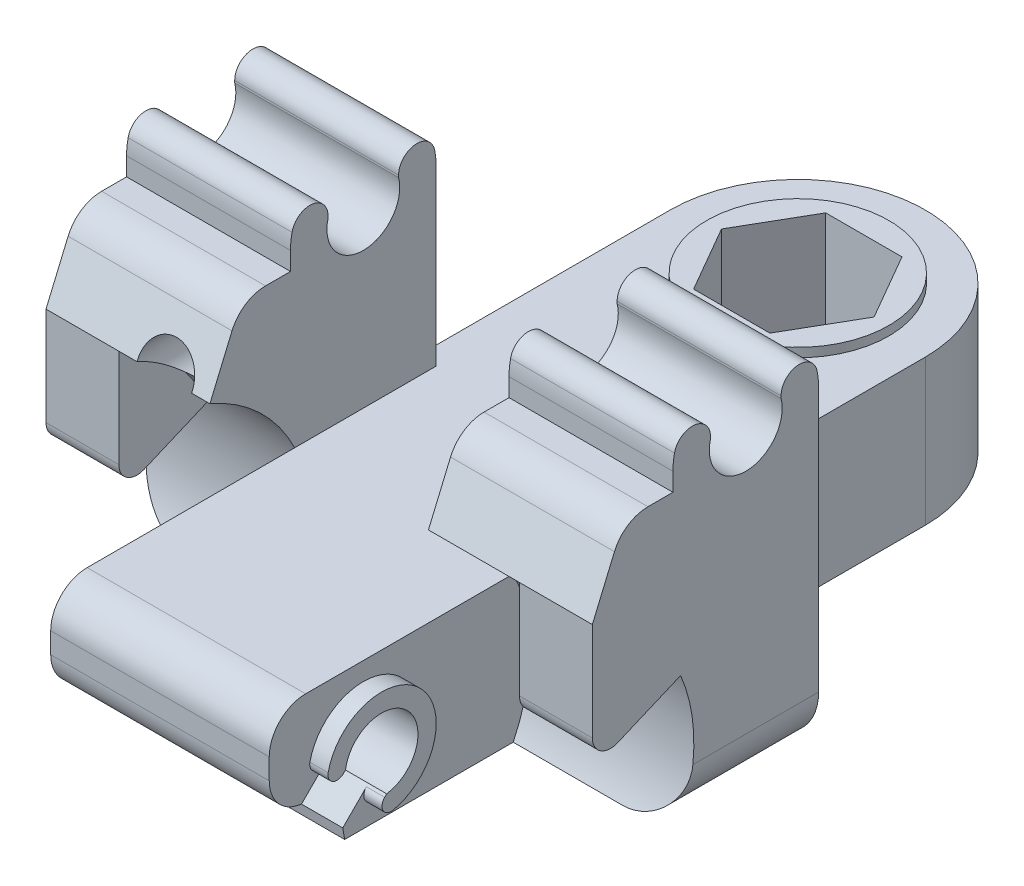
SolidWorks part; units mm, degrees
ref_plane "Front Plane" through (0, 0, 0) normal (0, 0, 1) x (1, 0, 0)
ref_plane "Top Plane" through (0, 0, 0) normal (0, 1, 0) x (1, 0, 0)
ref_plane "Right Plane" through (0, 0, 0) normal (1, 0, 0) x (0, 0, -1)
sketch "Sketch3" plane through (0, 0, 0) normal (1, 0, 0) x (0, 0, -1)
  line L0 (0.2828, -1.9799) -> (-1.9799, 0.2828)
  line L1 (0.2828, -1.9799) -> (-1.1314, -3.3941)
  line L2 (-1.1314, -3.3941) -> (-0.8188, -5.1668)
  line L3 (-0.8188, -5.1668) -> (-3.9199, -8.2678)
  line L4 (-1.9799, 0.2828) -> (-3.3941, -1.1314)
  line L5 (-3.3941, -1.1314) -> (-5.1668, -0.8188)
  line L6 (-5.1668, -0.8188) -> (-8.2678, -3.9199)
  line L7 (-0.8485, -0.8485) -> (0, 0) construction
  line L8 (0, 0) -> (-2, 0) construction
  line L9 (-1.9799, 0.2828) -> (-5.1668, -0.8188) construction
  line L10 (-0.8188, -5.1668) -> (0.2828, -1.9799) construction
  circle A0 centre (0, 0) radius 2
  circle A1 centre (0, 0) radius 8.65 construction
  circle A2 centre (0, 0) radius 9.15 construction
  circle A3 centre (0, 0) radius 9.15
  dimension "D1" = 4
  dimension "D2" = 17.3
  dimension "D4" = 0.5
  dimension "D5" = 2
  dimension "D7" = 3.2
  dimension "D6" = 1.8
  dimension "D8" = 45
  dimension "D9" = 125
extrude "Boss-Extrude1" add sketch "Sketch3" along normal mid plane 12 contours A3 L6 L5 L4 A0 L1 L2 L3 | A3 region at (0, -1.48, -1.7064)
sketch "Sketch5" plane through (0, 0, 0) normal (1, 0, 0) x (0, 0, -1)
  line L0 (0, 9.15) -> (29.856, 9.15)
  line L1 (29.856, 9.15) -> (29.856, -9.15)
  line L2 (29.856, -9.15) -> (0, -9.15)
  arc A0 (-3.9199, -8.2678) -> (-8.2678, -3.9199) centre (0, 0) ccw construction
  arc A1 (0, -9.15) -> (0, 9.15) centre (0, 0) ccw
  dimension "D1" = 29.856
extrude "Boss-Extrude2" add sketch "Sketch5" along normal mid plane 14
sketch "Sketch6" plane through (0, 9.15, 0) normal (0, 1, 0) x (1, 0, 0)
  line L0 (7, 29.856) -> (-7, 29.856) construction
  circle A0 centre (0, 29.856) radius 7
extrude "Boss-Extrude3" add sketch "Sketch6" against normal up to surface (18.3 mm away) up to face at (0, -9.15, -9.952)
sketch "Sketch7" plane through (0, 0, 0) normal (0, 1, 0) x (1, 0, 0)
  circle A0 centre (0, 29.856) radius 4.5
  dimension "D1" = 9
extrude "Boss-Extrude4" add sketch "Sketch7" along normal blind 8 and the other way blind 8
sketch "Sketch8" plane through (0, 9.15, 0) normal (0, 1, 0) x (1, 0, 0)
  line L0 (6, -9.15) -> (6, 0) construction
  line L1 (-6, 0) -> (-6, -9.15) construction
  line L3 (7, 0) -> (7, 29.856) construction
  line L4 (-7, 29.856) -> (-7, 0) construction
  line L5 (-7, 0) -> (-6, 0) construction
  line L6 (6, 0) -> (7, 0) construction
  line L7 (6, -9.15) -> (6, 0)
  line L8 (-6, 0) -> (-6, -9.15)
  line L9 (-6, -9.15) -> (6, -9.15)
  line L10 (7, 0) -> (7, 29.856)
  line L11 (-7, 29.856) -> (-7, 0)
  line L12 (-7, 0) -> (-6, 0)
  line L13 (6, 0) -> (7, 0)
  arc A0 (7, 29.856) -> (-7, 29.856) centre (0, 29.856) ccw construction
  arc A1 (7, 29.856) -> (-7, 29.856) centre (0, 29.856) ccw
  line M10 (7, 0) -> (7, 29.856)
  arc M11 (7, 29.856) -> (-7, 29.856) centre (0, 29.856) ccw
  line M12 (-7, 29.856) -> (-7, 0)
  line M13 (-7, 0) -> (-6, 0)
  line M14 (-6, 0) -> (6, 0)
  line M15 (6, 0) -> (7, 0)
extrude "Cut-Extrude2" cut sketch "Sketch8" against normal offset from surface (5.15 mm away) 4 contours M15 M10 M11 M12 M13 M14 | L8 L9 L7 M14 region at (0, 9.15, 4.575) region at (0, 9.15, -17.7114) up to plane "Top Plane"
sketch "Sketch9" plane through (0, -9.15, 0) normal (0, -1, 0) x (1, 0, 0)
  line L7 (6, 0) -> (6, 9.15)
  line L8 (7, 0) -> (6, 0)
  line L9 (7, -29.856) -> (7, 0)
  line L10 (-7, 0) -> (-7, -29.856)
  line L11 (-6, 0) -> (-7, 0)
  line L12 (-6, 9.15) -> (-6, 0)
  line L13 (6, 9.15) -> (-6, 9.15)
  line L14 (6, 0) -> (6, 9.15)
  line L15 (7, 0) -> (6, 0)
  line L16 (7, -29.856) -> (7, 0)
  line L17 (-7, 0) -> (-7, -29.856)
  line L18 (-6, 0) -> (-7, 0)
  line L19 (-6, 9.15) -> (-6, 0)
  line L20 (6, 9.15) -> (-6, 9.15)
  arc A1 (-7, -29.856) -> (7, -29.856) centre (0, -29.856) ccw
  arc A2 (-7, -29.856) -> (7, -29.856) centre (0, -29.856) ccw
  line M10 (-7, 0) -> (-7, -29.856)
  arc M11 (-7, -29.856) -> (7, -29.856) centre (0, -29.856) ccw
  line M12 (7, -29.856) -> (7, 0)
  line M13 (7, 0) -> (6, 0)
  line M14 (6, 0) -> (-6, 0)
  line M15 (-6, 0) -> (-7, 0)
  dimension "D1" = 0
extrude "Cut-Extrude4" cut sketch "Sketch9" against normal offset from surface (5.15 mm away) 4 contours M15 M10 M11 M12 M13 M14 | L14 L20 L19 M14 region at (0, -9.15, 4.575) region at (0, -9.15, -17.7114) up to plane "Top Plane"
sketch "Sketch24" plane through (-6, 0, 0) normal (-1, 0, 0) x (0, 0, 1)
  line L0 (1.9799, 0.2828) -> (2.9258, -0.6631)
  line L1 (1.9799, 0.2828) -> (3.3941, -1.1314) construction
  line L2 (-0.2828, -1.9799) -> (0.6631, -2.9258)
  line L3 (-0.2828, -1.9799) -> (1.1314, -3.3941) construction
  arc A0 (1.9799, 0.2828) -> (-0.2828, -1.9799) centre (0, 0) ccw construction
  arc A1 (1.9799, 0.2828) -> (-0.2828, -1.9799) centre (0, 0) ccw
  circle A2 centre (0, 0) radius 3
  line M5 (1.1314, -3.3941) -> (-0.2828, -1.9799)
  arc M6 (-0.2828, -1.9799) -> (1.9799, 0.2828) centre (0, 0) cw
  line M7 (1.9799, 0.2828) -> (3.3941, -1.1314)
  dimension "D1" = 6
extrude "Boss-Extrude6" add sketch "Sketch24" along normal blind 1 contours A2 M7 M5 M6 region at (-6, 1.4742, -1.4742)
fillet "Fillet3" radius 0.5 2 edges at (-6.5, -2.9258, 0.6631) (-6.5, -0.6631, 2.9258)
mirror "Mirror1" about plane through (0, 0, 0) normal (1, 0, 0) of "Fillet3", "Boss-Extrude6"
sketch "Sketch10" plane through (0, 0, 0) normal (1, 0, 0) x (0, 0, -1)
  line L3 (8.2294, -4) -> (29.856, -4)
  line L4 (29.856, -4) -> (29.856, 4)
  line L5 (29.856, 4) -> (8.2294, 4)
  line L10 (8, 12.5) -> (8, 17.5) construction
  line L11 (8, 17.5) -> (16, 17.5) construction
  line L12 (16, 17.5) -> (16, 4) construction
  line L13 (5.3059, 12.5) -> (8, 12.5)
  line L14 (0, 0) -> (3.5752, 8.4226) construction
  line L15 (3.5752, 8.4226) -> (5.3059, 12.5)
  line L16 (29.856, 4) -> (8.2294, 4) construction
  line L17 (16, 4) -> (8.2294, 4)
  line L18 (8, 13.5) -> (16, 13.5) construction
  line L19 (26, 14) -> (26, 4) construction
  line L20 (29.856, -4) -> (8.2294, -4) construction
  line L21 (10.0635, 14) -> (13.9365, 14) construction
  line L22 (13.9365, 14) -> (13.9365, 17)
  line L23 (10.0635, 17) -> (10.0635, 14)
  line L24 (8, 13.5) -> (8, 12.5)
  line L25 (16, 13.5) -> (16, 4)
  line L26 (16, -4) -> (8.2294, -4)
  line L27 (16, 4) -> (16, -4)
  arc A0 (10.0635, 14) -> (13.9365, 14) centre (12, 13.5) ccw
  arc A1 (8.2294, -4) -> (8.2294, 4) centre (0, 0) ccw
  arc A2 (8.2294, 4) -> (3.5752, 8.4226) centre (0, 0) ccw
  arc A3 (16, 13.5) -> (13.9365, 17) centre (12, 13.5) ccw
  arc A4 (10.0635, 17) -> (8, 13.5) centre (12, 13.5) ccw
  arc A5 (8.2294, -4) -> (8.2294, 4) centre (0, 0) ccw construction
  arc A6 (8.2294, -4) -> (8.2294, 4) centre (0, 0) ccw
  dimension "D8" = 4
  dimension "D9" = 2
  dimension "D10" = 2.5
  dimension "D2" = 67
  dimension "D3" = 10
  dimension "D4" = 13.5
  dimension "D5" = 5
  dimension "D6" = 12
  dimension "D7" = 5
  dimension "D1" = 0
extrude "Boss-Extrude5" add sketch "Sketch10" along normal mid plane 30 contours A6 L26 L27 L17 | L23 A4 L24 L13 L15 A2 L17 L25 A3 L22 A0 region at (0, 0, -12.4196) region at (0, 9.2496, -10.8111)
ref_plane "Plane1" through (6, 0, 0) normal (1, 0, 0) x (0, 0, -1)
ref_plane "Plane2" through (-6, 0, 0) normal (1, 0, 0) x (0, 0, -1)
sketch "Sketch13" plane through (-6, 0, 0) normal (1, 0, 0) x (0, 0, -1)
  line L0 (0, 5) -> (36.856, 5)
  line L2 (36.856, 4) -> (36.856, 5) construction
  circle A0 centre (0, 0) radius 5 construction
  dimension "D1" = 10
ref_plane "Plane3" through (0, 0, 0) normal (0, 0, 1) x (1, 0, 0)
ref_plane "Plane4" [suppressed] through (0, 0, -32.856) normal (0, 0, -1) x (-1, 0, 0)
ref_plane "Plane5" [suppressed] through (-3, 0, 0) normal (-1, 0, 0) x (0, 0, 1)
sketch "Sketch18" [suppressed] plane through (0, 0, -32.856) normal (0, 0, -1) x (-1, 0, 0)
  line L0 (0, 29) -> (0, 16) construction
  line L2 (3, 29) -> (-3, 29) construction
  circle A0 centre (0, 16) radius 1.9
  dimension "D2" = 3.8
  dimension "D1" = 13
extrude "Cut-Extrude5" [suppressed] cut sketch "Sketch18" against normal blind 1
sketch "Sketch20" plane through (0, 4, 0) normal (0, 1, 0) x (1, 0, 0)
  line L0 (0, 25.356) -> (0, 0) construction
  line L2 (-6, -16) -> (6, -16)
  line L3 (-6, -16) -> (-6, 16)
  line L4 (-6, 16) -> (6, 16)
  line L5 (6, -16) -> (6, 16)
  line L6 (-6, -16) -> (6, 16) construction
  line L7 (-6, 16) -> (6, -16) construction
  line L8 (-7, 16) -> (7, 16) construction
  dimension "D1" = 12
extrude "Cut-Extrude7" cut sketch "Sketch20" along normal through all
sketch "Sketch32" plane through (6, 0, 0) normal (1, 0, 0) x (0, 0, -1)
  line L0 (-5.1668, -0.8188) -> (-5.1668, 4)
  line L1 (8.2294, 4) -> (-8.2294, 4) construction
  line L9 (-3.3941, -1.1314) -> (-2.0905, 0.1722)
  line L10 (0.1722, -2.0905) -> (-1.1314, -3.3941)
  line L11 (-1.1314, -3.3941) -> (-1.0245, -4)
  line L12 (-1.0245, -4) -> (8.2294, -4)
  line L13 (8.2294, 4) -> (-8.2294, 4)
  line L14 (-8.2678, -3.9199) -> (-5.1668, -0.8188)
  line L15 (-5.1668, -0.8188) -> (-3.3941, -1.1314)
  line L16 (-3.3941, -1.1314) -> (-2.0905, 0.1722)
  line L17 (0.1722, -2.0905) -> (-1.1314, -3.3941)
  line L18 (-1.1314, -3.3941) -> (-1.0245, -4)
  line L19 (-1.0245, -4) -> (8.2294, -4)
  line L20 (8.2294, 4) -> (-8.2294, 4)
  line L21 (-8.2678, -3.9199) -> (-5.1668, -0.8188)
  line L22 (-5.1668, -0.8188) -> (-3.3941, -1.1314)
  arc A5 (-2.9329, 0.6309) -> (-2.0905, 0.1722) centre (-2.4441, 0.5258) ccw
  arc A6 (0.6309, -2.9329) -> (-2.9329, 0.6309) centre (0, 0) ccw
  arc A7 (0.1722, -2.0905) -> (0.6309, -2.9329) centre (0.5258, -2.4441) ccw
  arc A8 (8.2294, -4) -> (8.2294, 4) centre (0, 0) ccw
  arc A9 (-8.2294, 4) -> (-8.2678, -3.9199) centre (0, 0) ccw
  arc A10 (-2.9329, 0.6309) -> (-2.0905, 0.1722) centre (-2.4441, 0.5258) ccw
  arc A11 (0.6309, -2.9329) -> (-2.9329, 0.6309) centre (0, 0) ccw
  arc A12 (0.1722, -2.0905) -> (0.6309, -2.9329) centre (0.5258, -2.4441) ccw
  arc A13 (8.2294, -4) -> (8.2294, 4) centre (0, 0) ccw
  arc A14 (-8.2294, 4) -> (-8.2678, -3.9199) centre (0, 0) ccw
  line M21 (8.2294, 4) -> (-8.2294, 4)
  arc M22 (-8.2294, 4) -> (-8.2678, -3.9199) centre (0, 0) ccw
  line M23 (-8.2678, -3.9199) -> (-5.1668, -0.8188)
  dimension "D1" = 0
extrude "Cut-Extrude9" cut sketch "Sketch32" against normal blind 25 contours L0 M23 M21 M22 region at (6, 0.6087, 7.1825)
fillet "Fillet1" radius 2 2 edges at (0, 4, 5.1668) (0, -0.8188, 5.1668)
fillet "Fillet2" radius 1 4 edges at (-10.5, 17, -13.9365) (-10.5, 17, -10.0635) (10.5, 17, -10.0635) (10.5, 17, -13.9365)
sketch "Sketch23" plane through (0, 4, 0) normal (0, 1, 0) x (1, 0, 0)
  line L0 (-7, 29.856) -> (7, 29.856) construction
  line L1 (4.1881, 29.856) -> (2.094, 33.483)
  line L2 (2.094, 33.483) -> (-2.094, 33.483)
  line L3 (-2.094, 33.483) -> (-4.1881, 29.856)
  line L4 (-4.1881, 29.856) -> (-2.094, 26.229)
  line L5 (-2.094, 26.229) -> (2.094, 26.229)
  line L6 (2.094, 26.229) -> (4.1881, 29.856)
  line L7 (-7, 16) -> (-7, 29.856) construction
  circle A0 centre (0, 29.856) radius 3.627 construction
  dimension "D1" = 7.254
extrude "Cut-Extrude8" cut sketch "Sketch23" against normal through all
sketch "Sketch25" plane through (15, 0, 0) normal (1, 0, 0) x (0, 0, -1)
  line L0 (10.0635, 13) -> (13.9365, 13)
  arc A0 (10.0635, 14) -> (13.9365, 14) centre (12, 13.5) ccw construction
  arc A1 (10.0635, 14) -> (13.9365, 14) centre (12, 13.5) ccw
  arc M14 (13.9365, 14) -> (10.0635, 14) centre (12, 13.5) cw
  dimension "D1" = 1.5
extrude "Boss-Extrude7" [suppressed] add sketch "Sketch25" against normal blind 1 contours L0 M14
fillet "Fillet4" [suppressed] radius 0.5
mirror "Mirror2" [suppressed] about plane through (0, 0, 0) normal (1, 0, 0)
fillet "Fillet5" radius 3 2 edges at (15, -4, -12.1147) (-15, -4, -12.1147)
fillet "Fillet7" radius 2 2 edges at (-10.5, 12.5, -5.3059) (10.5, 12.5, -5.3059)
ref_plane "Plane6" through (-8.5, 0, 0) normal (-1, 0, 0) x (0, 0, 1)
sketch "Sketch27" plane through (-8.5, 0, 0) normal (-1, 0, 0) x (0, 0, 1)
  line L0 (0, 8.5) -> (-25.4214, 8.5)
  circle A0 centre (0, 0) radius 8.5 construction
  dimension "D1" = 17
sweep "Cut-Sweep1" cut path "Sketch27" circular profile diameter 3 parameters "D3"=3
sketch "Sketch28" plane through (15, 0, 0) normal (1, 0, 0) x (0, 0, -1)
  line L0 (0, 0) -> (8.4226, 3.5752) construction
  line L1 (8.4226, 3.5752) -> (3.5752, 1.5176)
  line L2 (0, 0) -> (0, 8.2854) construction
  line L3 (3.5752, 1.5176) -> (3.5752, 8.4226)
  arc A0 (9.0952, -1) -> (3.5752, 8.4226) centre (0, 0) ccw construction
  arc A1 (9.0952, -1) -> (3.5752, 8.4226) centre (0, 0) ccw
  arc M6 (3.5752, 8.4226) -> (9.0952, -1) centre (0, 0) cw
  dimension "D1" = 67
extrude "Boss-Extrude8" add sketch "Sketch28" against normal blind 4 contours L3 L1 M6 region at (15, 4.7658, -5.3454)
fillet "Fillet8" radius 1 1 edges at (13, 1.5176, -3.5752)
mirror "Mirror3" about plane through (0, 0, 0) normal (1, 0, 0) of "Fillet8", "Boss-Extrude8"
sketch "Sketch33" plane through (0, 4, 0) normal (0, 1, 0) x (1, 0, 0)
  line L0 (4.1881, 29.856) -> (2.094, 33.483) construction
  line L1 (2.094, 26.229) -> (4.1881, 29.856) construction
  line L2 (-2.094, 26.229) -> (2.094, 26.229) construction
  line L3 (-4.1881, 29.856) -> (-2.094, 26.229) construction
  line L4 (-2.094, 33.483) -> (-4.1881, 29.856) construction
  line L5 (2.094, 33.483) -> (-2.094, 33.483) construction
  line L6 (4.1881, 29.856) -> (2.094, 33.483)
  line L7 (2.094, 26.229) -> (4.1881, 29.856)
  line L8 (-2.094, 26.229) -> (2.094, 26.229)
  line L9 (-4.1881, 29.856) -> (-2.094, 26.229)
  line L10 (-2.094, 33.483) -> (-4.1881, 29.856)
  line L11 (2.094, 33.483) -> (-2.094, 33.483)
  arc A0 (7, 29.856) -> (-7, 29.856) centre (0, 29.856) ccw construction
  arc A1 (7, 29.856) -> (-7, 29.856) centre (0, 29.856) ccw
  circle A2 centre (0, 29.856) radius 5
  line M8 (4.1881, 29.856) -> (2.094, 26.229)
  line M9 (2.094, 26.229) -> (-2.094, 26.229)
  line M10 (-2.094, 26.229) -> (-4.1881, 29.856)
  line M11 (-4.1881, 29.856) -> (-2.094, 33.483)
  line M12 (-2.094, 33.483) -> (2.094, 33.483)
  line M13 (2.094, 33.483) -> (4.1881, 29.856)
  dimension "D1" = 10
extrude "Boss-Extrude9" add sketch "Sketch33" along normal blind 0.5 contours A2 M13 M8 M9 M10 M11 M12 region at (-4.8586, 4, -29.856)
ref_plane "Plane7" through (0, 0, 0) normal (0, -1, 0) x (-1, 0, 0)
